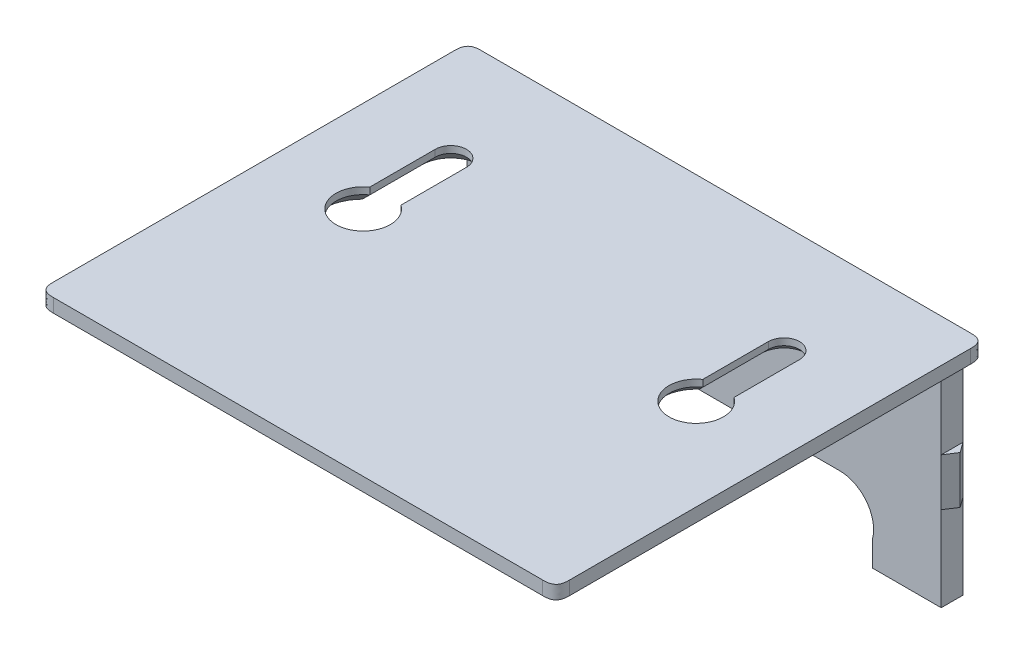
SolidWorks part; units mm, degrees
ref_plane "Front Plane" through (0, 0, 0) normal (0, 0, 1) x (1, 0, 0)
ref_plane "Top Plane" through (0, 0, 0) normal (0, 1, 0) x (1, 0, 0)
ref_plane "Right Plane" through (0, 0, 0) normal (1, 0, 0) x (0, 0, -1)
sketch "Sketch1" plane through (0, 0, 0) normal (0, 1, 0) x (1, 0, 0)
  line L1 (-38, 31.5) -> (38, 31.5)
  line L2 (-38, 31.5) -> (-38, -31.5)
  line L3 (-38, -31.5) -> (38, -31.5)
  line L4 (38, 31.5) -> (38, -31.5)
  line L5 (0, -31.5) -> (0, 31.5) construction
  line L6 (-38, 0) -> (38, 0) construction
  point P0 (0, 0)
  dimension "D1" = 76
  dimension "D2" = 63
extrude "Boss-Extrude1" add sketch "Sketch1" along normal blind 2
sketch "Sketch2" plane through (0, 0, 0) normal (0, 1, 0) x (1, 0, 0)
  line L0 (38, 31.5) -> (-38, 31.5) construction
  line L1 (-34.8, -28.3) -> (34.8, -28.3)
  line L2 (-34.8, -28.3) -> (-34.8, 28.3)
  line L3 (-34.8, 28.3) -> (34.8, 28.3)
  line L4 (34.8, -28.3) -> (34.8, 28.3)
  line L5 (0, 28.3) -> (0, -28.3) construction
  line L6 (-34.8, 0) -> (34.8, 0) construction
  line L7 (-38, 31.5) -> (-38, -31.5) construction
  point P0 (0, 0)
  dimension "D1" = 3.2
  dimension "D2" = 3.2
extrude "Boss-Extrude2" add sketch "Sketch2" against normal blind 1
sketch "Sketch3" plane through (0, 0, 0) normal (0, -1, 0) x (1, 0, 0)
  line L0 (38, -31.5) -> (-38, -31.5) construction
  line L1 (-34.9, -31.5) -> (34.9, -31.5)
  line L2 (-34.9, -31.5) -> (-34.9, -28.3)
  line L3 (-34.9, -28.3) -> (34.9, -28.3)
  line L4 (34.9, -31.5) -> (34.9, -28.3)
  line L5 (0, -28.3) -> (0, -31.5) construction
  line L6 (-34.9, -29.9) -> (34.9, -29.9) construction
  line L7 (34.8, -28.3) -> (-34.8, -28.3) construction
  line L8 (-38, -31.5) -> (-38, 31.5) construction
  line L9 (38, 31.5) -> (38, -31.5) construction
  point P560 (0, -29.9)
  dimension "D1" = 3.1
  dimension "D2" = 3.1
extrude "Boss-Extrude3" add sketch "Sketch3" along normal blind 32
ref_plane "Plane1" through (0, 0, -1.5) normal (0, 0, 1) x (1, 0, 0)
sketch "Sketch4" plane through (0, 0, -1.5) normal (0, 0, 1) x (1, 0, 0)
  line L0 (-34.8, 0) -> (-36, -1.5)
  line L1 (-36, -1.5) -> (-34.8, -3)
  line L2 (-34.8, -3) -> (-33.3, -3)
  line L3 (-33.3, -3) -> (-33.3, 0)
  line L4 (-34.8, 0) -> (34.8, 0) construction
  line L5 (-33.3, 0) -> (-34.8, 0)
  line L6 (0, 0) -> (0, -13.9424) construction
  line L7 (33.3, 0) -> (34.8, 0)
  line L8 (33.3, -3) -> (33.3, 0)
  line L9 (34.8, -3) -> (33.3, -3)
  line L10 (36, -1.5) -> (34.8, -3)
  line L11 (34.8, 0) -> (36, -1.5)
  dimension "D1" = 1.5
  dimension "D2" = 3
  dimension "D3" = 1.2
  dimension "D4" = 1.5
extrude "Boss-Extrude4" add sketch "Sketch4" along normal mid plane 7
sketch "Sketch5" plane through (0, 0, 0) normal (1, 0, 0) x (0, 0, -1)
  line L0 (-28.3, 0) -> (-29.5, -1.5)
  line L1 (-29.5, -1.5) -> (-28.3, -3)
  line L2 (-28.3, -3) -> (-27.3, -3)
  line L3 (-27.3, -3) -> (-27.3, 0)
  line L4 (-31.5, 0) -> (31.5, 0) construction
  line L5 (-27.3, 0) -> (-28.3, 0)
  dimension "D1" = 1
  dimension "D2" = 1.2
  dimension "D3" = 3
  dimension "D4" = 1.5
extrude "Boss-Extrude5" add sketch "Sketch5" along normal mid plane 7
ref_plane "Plane2" through (0, -16, 0) normal (0, -1, 0) x (-1, 0, 0)
sketch "Sketch6" plane through (0, -16, 0) normal (0, -1, 0) x (-1, 0, 0)
  line L0 (-34.9, 31.5) -> (-36, 30)
  line L1 (-36, 30) -> (-34.9, 28.3)
  line L2 (-34.9, 28.3) -> (-34.9, 31.5)
  line L3 (0, 0) -> (0, 15.5484) construction
  line L4 (34.9, 28.3) -> (34.9, 31.5)
  line L5 (36, 30) -> (34.9, 28.3)
  line L6 (34.9, 31.5) -> (36, 30)
  dimension "D1" = 1.1
  dimension "D2" = 1.5
extrude "Boss-Extrude6" add sketch "Sketch6" along normal mid plane 7
sketch "Sketch7" plane through (0, -1, 0) normal (0, -1, 0) x (1, 0, 0)
  line L0 (-26.822, -5.8793) -> (-26.822, -15.5165)
  line L1 (-22.222, -5.8793) -> (-22.222, -15.5165)
  line L2 (0, 0) -> (0, 14.6331) construction
  line L3 (22.222, -5.8793) -> (22.222, -15.5165)
  line L4 (26.822, -5.8793) -> (26.822, -15.5165)
  arc A0 (-26.822, -5.8793) -> (-22.222, -5.8793) centre (-24.522, -2.6067) cw
  arc A1 (-22.222, -15.5165) -> (-26.822, -15.5165) centre (-24.522, -15.5165) cw
  arc A2 (22.222, -15.5165) -> (26.822, -15.5165) centre (24.522, -15.5165) ccw
  arc A3 (26.822, -5.8793) -> (22.222, -5.8793) centre (24.522, -2.6067) ccw
  dimension "D1" = 2.3
  dimension "D2" = 4
extrude "Cut-Extrude1" cut sketch "Sketch7" against normal blind 7
chamfer "Chamfer1" distance 2 angle 45 8 edges at (26.822, -1, -10.6979) (24.522, -1, -17.8165) (22.222, -1, -10.6979) (24.522, -1, 1.3933) (-22.222, -1, -10.6979) (-24.522, -1, -17.8165) (-26.822, -1, -10.6979) (-24.522, -1, 1.3933)
fillet "Fillet1" radius 2 4 edges at (38, 1, 31.5) (38, 1, -31.5) (-38, 1, 31.5) (-38, 1, -31.5) curvature continuous yes
sketch "Sketch8" plane through (0, 0, -31.5) normal (0, 0, -1) x (-1, 0, 0)
  line L0 (-34.9, -20) -> (34.9, -20) construction
  line L1 (-34.9, -32) -> (-34.9, -19.5) construction
  line L2 (34.9, -32) -> (34.9, -19.5) construction
  line L3 (34.9, -32) -> (-34.9, -32) construction
  line L4 (-19.9507, -27) -> (-11.9507, -27) construction
  line L5 (-19.9507, -22) -> (-11.9507, -22)
  line L6 (-19.9507, -32) -> (-11.9507, -32)
  line L7 (34.9, -12.5) -> (34.9, 0) construction
  line L8 (-34.9, -12.5) -> (-34.9, 0) construction
  line L9 (-27.4, 0.5) -> (-15.4, 0.5)
  line L10 (-27.4, 0.5) -> (-27.4, -8.5)
  line L11 (-27.4, -8.5) -> (-15.4, -8.5)
  line L12 (-15.4, 0.5) -> (-15.4, -8.5)
  line L13 (-21.4, -8.5) -> (-21.4, 0.5) construction
  line L14 (-27.4, -4) -> (-15.4, -4) construction
  arc A0 (-19.9507, -22) -> (-19.9507, -32) centre (-19.9507, -27) ccw
  arc A1 (-11.9507, -32) -> (-11.9507, -22) centre (-11.9507, -27) ccw
  circle A2 centre (14.4, -21.8) radius 7
  point P10 (-15.9507, -27)
  point P25 (-19.9507, -25.921)
  point P211 (-21.4, -4)
  dimension "D2" = 5
  dimension "D6" = 14
  dimension "D1" = 12
  dimension "D4" = 8
  dimension "D7" = 20.5
  dimension "D8" = 1.8
  dimension "D9" = 12
  dimension "D10" = 9
  dimension "D11" = 16
  dimension "D12" = 13.5
extrude "Cut-Extrude2" cut sketch "Sketch8" against normal up to surface (3.2 mm away) and the other way through all from offset 0 up to face at (0, -10.8333, -28.3)
sketch "Sketch9" plane through (0, -1, 0) normal (0, -1, 0) x (1, 0, 0)
  line L0 (34.8, -28.3) -> (27.4, -28.3) construction
  line L1 (15.4, -28.3) -> (33.261, -28.3)
  line L2 (15.4, -28.3) -> (15.4, -0.3)
  line L3 (15.4, -0.3) -> (33.261, -0.3)
  line L4 (33.261, -28.3) -> (33.261, -0.3)
  line L5 (24.3305, -0.3) -> (24.3305, -28.3) construction
  line L6 (15.4, -14.3) -> (33.261, -14.3) construction
  point P412 (24.3305, -14.3)
  dimension "D1" = 28
extrude "Cut-Extrude3" cut sketch "Sketch9" against normal blind 1
sketch "Sketch10" plane through (0, -1, 0) normal (0, -1, 0) x (1, 0, 0)
  line L0 (34.8, 28.3) -> (34.8, 2) construction
  line L1 (-34.8, 27.3) -> (34.8, 27.3)
  line L2 (-34.8, 27.3) -> (-34.8, 19.3)
  line L3 (-34.8, 19.3) -> (34.8, 19.3)
  line L4 (34.8, 27.3) -> (34.8, 19.3)
  line L5 (0, 19.3) -> (0, 27.3) construction
  line L6 (-34.8, 23.3) -> (34.8, 23.3) construction
  line L8 (3.5, 27.3) -> (-3.5, 27.3) construction
  line L9 (-34.8, 2) -> (-34.8, 28.3) construction
  line L10 (34.8, 28.3) -> (34.8, 2) construction
  point P128 (0, 23.3)
  dimension "D1" = 8
extrude "Cut-Extrude4" cut sketch "Sketch10" against normal blind 2
chamfer "Chamfer2" distance 1 angle 60 1 edges at (0, -3, 27.3) first distance on face at (0, -3, 27.8)
sketch "Sketch11" plane through (0, 0, -31.5) normal (0, 0, -1) x (-1, 0, 0)
  line L0 (-24.7989, -28.2226) -> (-24.7989, -36.2743)
  line L1 (-24.7989, -36.2743) -> (17.4169, -36.2743)
  line L2 (17.4169, -36.2743) -> (17.4169, -28.1165)
  line L3 (-24.7989, -28.2226) -> (-13.0829, -28.2226)
  line L4 (-13.0829, -28.2226) -> (-13.0829, -22)
  line L5 (-19.9507, -22) -> (-11.9507, -22) construction
  line L6 (-13.0829, -22) -> (7.4029, -22)
  line L7 (7.4029, -22) -> (17.4169, -28.1165)
  circle A1 centre (14.4, -21.8) radius 7 construction
  arc A2 (-19.9507, -22) -> (-19.9507, -32) centre (-19.9507, -27) ccw construction
  point P2 (-24.4358, -28.131)
extrude "Cut-Extrude5" cut sketch "Sketch11" against normal up to surface (3.2 mm away) up to face at (9.8148, -11.6818, -28.3)
